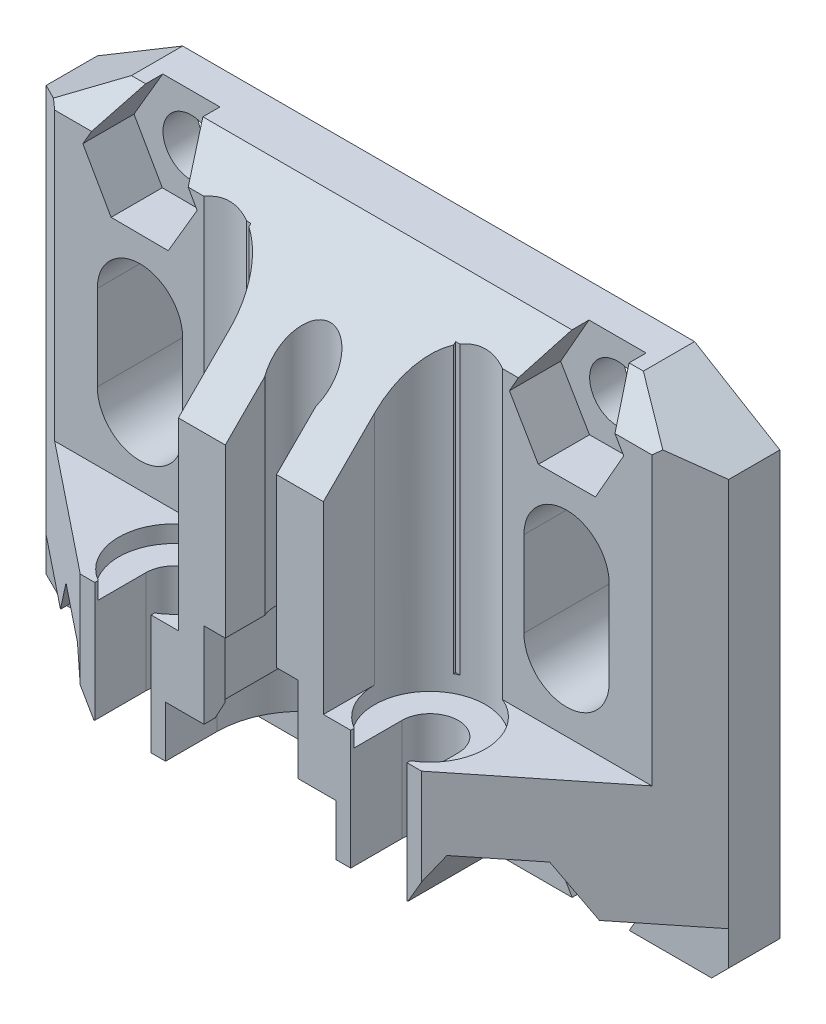
SolidWorks part; units mm, degrees
ref_plane "Front Plane" through (0, 0, 0) normal (0, 0, 1) x (1, 0, 0)
ref_plane "Top Plane" through (0, 0, 0) normal (0, 1, 0) x (1, 0, 0)
ref_plane "Right Plane" through (0, 0, 0) normal (1, 0, 0) x (0, 0, -1)
sketch "Sketch1" plane through (0, 0, 0) normal (0, 0, 1) x (1, 0, 0)
  line L1 (-20, 0) -> (20, 0)
  line L2 (-20, 0) -> (-20, 28.8)
  line L3 (-20, 28.8) -> (20, 28.8)
  line L4 (20, 0) -> (20, 28.8)
  dimension "D2" = 40
  dimension "D3" = 28.8
extrude "Boss-Extrude1" add sketch "Sketch1" along normal blind 11
chamfer "Chamfer2" distance 8 distance2 8 1 edges at (0, 28.8, 11)
sketch "Sketch10" plane through (0, 0, 11) normal (0, 0, 1) x (1, 0, 0)
  line L0 (-6, 28.8) -> (-6, 10)
  line L2 (-6, 10) -> (-20, 10)
  line L3 (-20, 20.8) -> (-20, 0) construction
  line L4 (0, 0) -> (0, 29.2248) construction
  line L5 (-6, 28.8) -> (-20, 28.8)
  line L6 (-20, 28.8) -> (-20, 10)
  line L7 (20, 28.8) -> (20, 10)
  line L8 (6, 28.8) -> (20, 28.8)
  line L9 (6, 10) -> (20, 10)
  line L10 (6, 28.8) -> (6, 10)
  line L11 (-20, 28.8) -> (20, 28.8) construction
  dimension "D1" = 10
  dimension "D2" = 6
extrude "Cut-Extrude7" cut sketch "Sketch10" against normal offset from surface (6 mm away) 5 up to face at (0, 14.4, 0)
sketch "Sketch11" plane through (0, 0, 11) normal (0, 0, 1) x (1, 0, 0)
  line L0 (20, 0) -> (20, 10) construction
  line L1 (-20, 0) -> (20, 0)
  line L2 (-20, 0) -> (-20, 3)
  line L3 (-20, 3) -> (20, 3)
  line L4 (20, 0) -> (20, 3)
  dimension "D1" = 3
extrude "Cut-Extrude8" cut sketch "Sketch11" against normal blind 8
chamfer "Chamfer3" distance 8 distance2 10 2 edges at (-20, 6.5, 11) (20, 6.5, 11) first distance on face at (-20, 12.2667, 4.5556) first distance on face at (20, 12.2667, 4.5556)
sketch "Sketch12" plane through (0, 28.8, 0) normal (0, 1, 0) x (1, 0, 0)
  line L0 (0, 0) -> (0, -14.4613) construction
  line L1 (-4.25, -8) -> (-4.25, -11)
  line L2 (-4.25, -11) -> (-10.75, -11)
  line L3 (-10, -11) -> (-6, -11) construction
  line L4 (-10.75, -11) -> (-10.75, -8)
  line L5 (6, -11) -> (-6, -11) construction
  arc A0 (-4.25, -8) -> (-10.75, -8) centre (-7.5, -8) ccw
  dimension "D1" = 3.25
  dimension "D2" = 8
  dimension "D3" = 7.5
extrude "Cut-Extrude9" cut sketch "Sketch12" against normal up to surface (18.8 mm away) up to face at (-9.875, 10, 8)
sketch "Sketch13" plane through (0, 10, 0) normal (0, 1, 0) x (1, 0, 0)
  line L0 (-9.15, -8) -> (-9.15, -11)
  line L1 (-10, -11) -> (-4.25, -11) construction
  line L2 (-9.15, -11) -> (-5.85, -11)
  line L3 (-5.85, -8) -> (-5.85, -11)
  arc A0 (-5.85, -8) -> (-9.15, -8) centre (-7.5, -8) ccw
  arc A1 (-4.25, -8) -> (-6, -5.1169) centre (-7.5, -8) ccw construction
  dimension "D1" = 3.3
extrude "Cut-Extrude10" cut sketch "Sketch13" against normal through all
sketch "Sketch3" plane through (0, 0, 0) normal (0, -1, 0) x (1, 0, 0)
  line L0 (0, 0) -> (0, 11) construction
  line L1 (-20, 11) -> (20, 11) construction
  line L2 (-5, 8) -> (-5, 11)
  line L3 (5, 8) -> (5, 11)
  line L4 (-5, 11) -> (5, 11)
  line L5 (-20, 0) -> (20, 0) construction
  arc A0 (-5, 8) -> (5, 8) centre (0, 8) ccw
  dimension "D1" = 8
  dimension "D2" = 10
extrude "Cut-Extrude2" cut sketch "Sketch3" against normal blind 6
sketch "Sketch4" plane through (0, 0, 11) normal (0, 0, 1) x (1, 0, 0)
  line L0 (0, 28.8) -> (0, 14.0803) construction
  line L1 (20, 28.8) -> (-20, 28.8) construction
  line L2 (-4, 20.8) -> (-4, 28.8)
  line L3 (4, 20.8) -> (4, 28.8)
  line L4 (-4, 28.8) -> (4, 28.8)
  arc A0 (-4, 20.8) -> (4, 20.8) centre (0, 20.8) ccw
  dimension "D2" = 4
  dimension "D1" = 8
extrude "Cut-Extrude3" [suppressed] cut sketch "Sketch4" against normal through all
sketch "Sketch2" plane through (0, 0, 11) normal (0, 0, 1) x (1, 0, 0)
  line L0 (0, 0) -> (0, 28.8) construction
  line L1 (20, 28.8) -> (-20, 28.8) construction
  line L2 (-12.5, 2.9) -> (12.5, 2.9) construction
  line L3 (-12.5, 25.9) -> (12.5, 25.9) construction
  line L4 (-12.5, 25.9) -> (-12.5, 2.9) construction
  circle A0 centre (-12.5, 2.9) radius 1.65
  circle A1 centre (12.5, 2.9) radius 1.65
  circle A2 centre (12.5, 25.9) radius 1.65
  circle A3 centre (-12.5, 25.9) radius 1.65
  dimension "D5" = 3.3
  dimension "D1" = 25
  dimension "D2" = 23
  dimension "D3" = 2.9
  dimension "D4" = 12.5
extrude "Cut-Extrude1" cut sketch "Sketch2" against normal through all
sketch "Sketch5" plane through (0, 0, 11) normal (0, 0, 1) x (1, 0, 0)
  line L0 (-13.8255, 29.3763) -> (-11.1423, 29.3763)
  line L1 (-9.1514, 25.8801) -> (-11.1423, 29.3763)
  line L2 (11.1423, 29.3763) -> (13.8255, 29.3763)
  line L3 (-13.8255, 29.3763) -> (-15.8486, 25.9199)
  line L4 (-15.8486, 25.9199) -> (-14.1916, 23.01)
  line L5 (-14.1916, 23.01) -> (-10.843, 22.9901)
  line L6 (-10.843, 22.9901) -> (-9.1514, 25.8801)
  line L19 (15.8486, 25.9199) -> (13.8255, 29.3763)
  line L21 (11.1423, 29.3763) -> (9.1514, 25.8801)
  line L22 (9.1514, 25.8801) -> (10.843, 22.9901)
  line L23 (10.843, 22.9901) -> (14.1916, 23.01)
  line L24 (14.1916, 23.01) -> (15.8486, 25.9199)
  line L26 (-10.81, 28.79) -> (-14.1585, 28.8099) [skipped]
  line L27 (14.1585, 28.8099) -> (10.81, 28.79) [skipped]
  circle A0 centre (-12.5, 25.9) radius 2.9 construction
  circle A3 centre (12.5, 25.9) radius 2.9 construction
  dimension "D1" = 5.8
extrude "Cut-Extrude4" cut sketch "Sketch5" against normal offset from surface (9 mm away) 2 up to face at (-10.85, 25.9, 0)
sketch "Sketch6" plane through (0, 6, 0) normal (0, -1, 0) x (1, 0, 0)
  line L0 (0, 0) -> (0, 11) construction
  line L1 (5, 11) -> (-5, 11) construction
  line L2 (-2.75, 11) -> (2.75, 11)
  line L3 (0, 4.6514) -> (2.9, 6.3257)
  line L4 (2.9, 6.3257) -> (2.9, 9.6743)
  line L5 (-2.9, 9.6743) -> (-2.75, 9.7609)
  line L6 (2.9, 9.6743) -> (2.75, 9.7609)
  line L7 (-2.9, 9.6743) -> (-2.9, 6.3257)
  line L8 (-2.9, 6.3257) -> (0, 4.6514)
  line L9 (-2.75, 9.7609) -> (-2.75, 11)
  line L10 (0, 11.3486) -> (-2.9, 9.6743) [skipped]
  line L11 (2.9, 9.6743) -> (0, 11.3486) [skipped]
  line L12 (2.75, 9.7609) -> (2.75, 11)
  circle A0 centre (0, 8) radius 2.9 construction
  dimension "D2" = 5.8
  dimension "D3" = 5.5
  dimension "D1" = 8
extrude "Cut-Extrude5" cut sketch "Sketch6" against normal blind 5
sketch "Sketch7" plane through (0, 11, 0) normal (0, -1, 0) x (1, 0, 0)
  line L0 (0, 0) -> (0, 11) construction
  line L1 (2.75, 11) -> (-2.75, 11) construction
  line L2 (-1.5, 8.6874) -> (-1.5, 11)
  line L3 (-1.5, 11) -> (1.5, 11)
  line L4 (1.5, 11) -> (1.5, 8.6874)
  arc A0 (-1.5, 8.6874) -> (1.5, 8.6874) centre (0, 8) ccw
  dimension "D1" = 3.3
  dimension "D2" = 8
  dimension "D3" = 3
  dimension "D4" = 1.5
extrude "Cut-Extrude6" cut sketch "Sketch7" against normal through all
sketch "Sketch15" plane through (0, 10, 0) normal (0, 1, 0) x (1, 0, 0)
  circle A0 centre (-7.5, -8) radius 3.25
extrude "Cut-Extrude12" cut sketch "Sketch15" against normal blind 1
sketch "Sketch16" plane through (0, 0, 5) normal (0, 0, 1) x (1, 0, 0)
  line L0 (-12.5, 25.9) -> (-12.5, 2.9) construction
  line L1 (-15, 14) -> (-15, 19)
  line L2 (-10, 14) -> (-10, 19)
  arc A0 (-10, 19) -> (-15, 19) centre (-12.5, 19) ccw
  arc A1 (-15, 14) -> (-10, 14) centre (-12.5, 14) ccw
  dimension "D1" = 2.5
  dimension "D2" = 14
  dimension "D3" = 19
extrude "Cut-Extrude13" cut sketch "Sketch16" against normal through all
mirror "Mirror1" about plane through (0, 0, 0) normal (1, 0, 0) of "Cut-Extrude13", "Cut-Extrude10", "Cut-Extrude9", "Cut-Extrude12"
chamfer "Chamfer4" distance 3 distance2 5 1 edges at (20, 28.8, 1.5) first distance on face at (20, 12.12, 1.8)
chamfer "Chamfer5" distance 5 distance2 3 1 edges at (-20, 28.8, 1.5) first distance on face at (-0.8333, 28.8, 2.1667)
chamfer "Chamfer6" [suppressed] distance 7 distance2 4 tangent propagation no
chamfer "Chamfer7" [suppressed] distance 4 distance2 7
sketch "Sketch14" plane through (0, 0, 11) normal (0, 0, 1) x (1, 0, 0)
  line L1 (-9.1514, 2.9) -> (-10.8257, 5.8)
  line L2 (-10.8257, 5.8) -> (-14.1743, 5.8)
  line L3 (-14.1743, 5.8) -> (-15.8486, 2.9)
  line L4 (-15.8486, 2.9) -> (-14.1743, 0)
  line L5 (-14.1743, 0) -> (-10.8257, 0)
  line L6 (-10.8257, 0) -> (-9.1514, 2.9)
  line L7 (15.8486, 2.9) -> (14.1743, 5.8)
  line L8 (14.1743, 5.8) -> (10.8257, 5.8)
  line L9 (10.8257, 5.8) -> (9.1514, 2.9)
  line L10 (9.1514, 2.9) -> (10.8257, 0)
  line L11 (10.8257, 0) -> (14.1743, 0)
  line L12 (14.1743, 0) -> (15.8486, 2.9)
  circle A0 centre (-12.5, 2.9) radius 2.9 construction
  circle A1 centre (12.5, 2.9) radius 2.9 construction
  arc A2 (-14.147, 3) -> (-10.853, 3) centre (-12.5, 2.9) ccw construction
  arc A3 (10.853, 3) -> (14.147, 3) centre (12.5, 2.9) ccw construction
  dimension "D1" = 5.8
extrude "Cut-Extrude11" cut sketch "Sketch14" against normal offset from surface (9.4 mm away) 1.6 up to face at (0, 18.2, 0)
chamfer "Chamfer8" distance 1 angle 45 2 edges at (-20, 0, 1.5) (20, 0, 1.5)
chamfer "Chamfer9" distance 0.5 angle 45 6 edges at (-2.825, 6, 9.7176) (-2.9, 6, 8) (-1.45, 6, 5.4885) (1.45, 6, 5.4885) (2.9, 6, 8) (2.825, 6, 9.7176)
chamfer "Chamfer10" [suppressed] distance 4 angle 25
